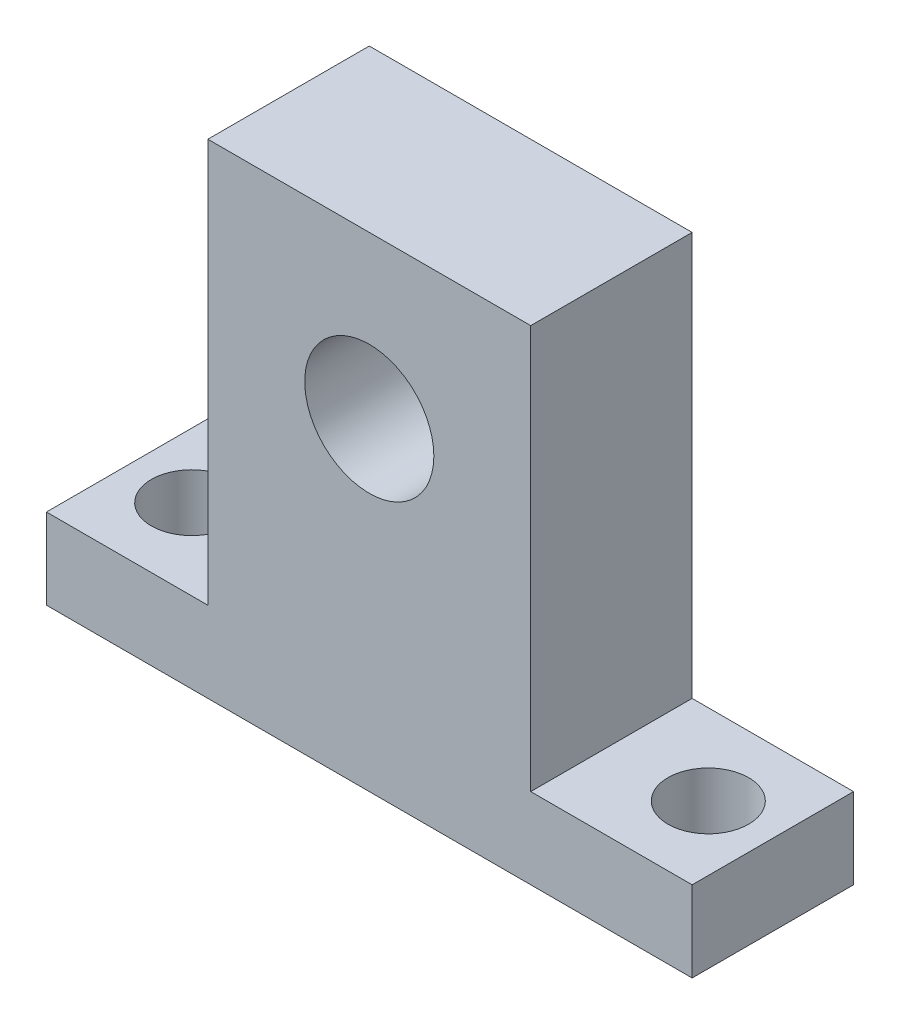
SolidWorks part; units mm, degrees
ref_plane "Plano frontal" through (0, 0, 0) normal (0, 0, 1) x (1, 0, 0)
ref_plane "Plano superior" through (0, 0, 0) normal (0, 1, 0) x (1, 0, 0)
ref_plane "Plano direito" through (0, 0, 0) normal (1, 0, 0) x (0, 0, -1)
sketch "Esboço1" plane through (0, 0, 0) normal (0, 0, 1) x (1, 0, 0)
  line L0 (-10, 10) -> (-10, -15)
  line L1 (-10, -15) -> (-20, -15)
  line L2 (-20, -15) -> (-20, -20)
  line L3 (-20, -20) -> (20, -20)
  line L4 (20, -20) -> (20, -15)
  line L5 (20, -15) -> (10, -15)
  line L6 (10, -15) -> (10, 10)
  line L7 (10, 10) -> (-10, 10)
  point P8 (0, 0)
  point P9 (0, 0)
  point P10 (0, 0)
  point P11 (0, 0)
  point P12 (0, 0)
  point P13 (0, 0)
  point P14 (0, 0)
  point P15 (0, 0)
  point P16 (0, 0)
  point P17 (0, 0)
  point P18 (0, 0)
  point P19 (0, 0)
  point P20 (0, 0)
  point P21 (0, 0)
  point P22 (0, 0)
  point P23 (0, 0)
  point P24 (0, 0)
  point P25 (0, 0)
  point P26 (0, 0)
  point P27 (0, 0)
  point P28 (0, 0)
  point P29 (0, 0)
  point P30 (0, 0)
extrude "Ressalto-extrusão1" add sketch "Esboço1" along normal blind 5 and the other way blind 5
sketch "Esboço2" plane through (0, 0, 0) normal (0, 0, 1) x (1, 0, 0)
  circle A0 centre (0, 0) radius 4
extrude "Corte-extrusão1" cut sketch "Esboço2" against normal blind 5 and the other way blind 5
sketch "Esboço3" plane through (0, 0, 0) normal (0, 1, 0) x (1, 0, 0)
  circle A0 centre (-16, 0) radius 2.5
  circle A1 centre (16, 0) radius 2.5
extrude "Corte-extrusão2" cut sketch "Esboço3" against normal through all
